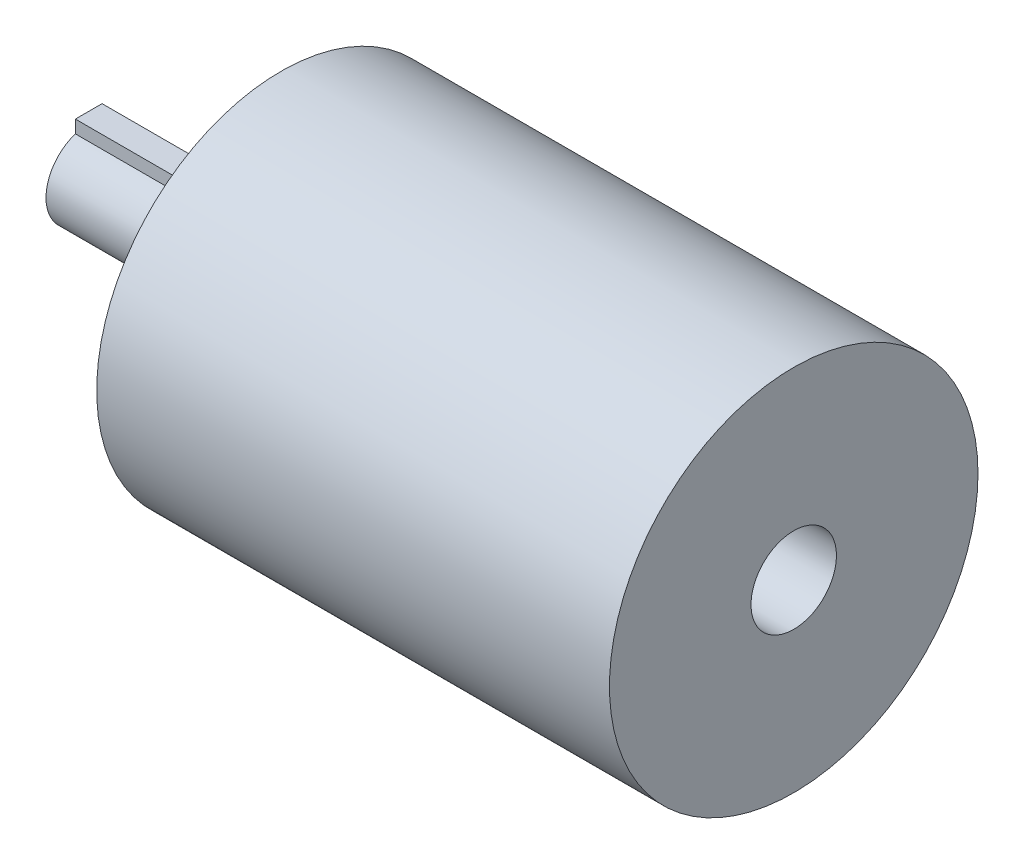
SolidWorks part; units mm, degrees
ref_plane "Front Plane" through (0, 0, 0) normal (0, 0, 1) x (1, 0, 0)
ref_plane "Top Plane" through (0, 0, 0) normal (0, 1, 0) x (1, 0, 0)
ref_plane "Right Plane" through (0, 0, 0) normal (1, 0, 0) x (0, 0, -1)
sketch "Sketch1" plane through (0, 0, 0) normal (1, 0, 0) x (0, 0, -1)
  line L1 (2.5, 10) -> (-2.5, 10)
  line L2 (2.5, 10) -> (2.5, 6)
  line L3 (2.5, 6) -> (-2.5, 6)
  line L4 (-2.5, 10) -> (-2.5, 6)
  line L5 (2.5, 10) -> (-2.5, 6) construction
  line L6 (2.5, 6) -> (-2.5, 10) construction
  circle A0 centre (0, 0) radius 26
  circle A1 centre (0, 0) radius 34.5
  circle A2 centre (0, 0) radius 8
  point P5 (0, 8)
  dimension "D1" = 69
  dimension "D4" = 16
  dimension "D5" = 52
  dimension "D2" = 5
  dimension "D3" = 4
extrude "Boss-Extrude1" add sketch "Sketch1" against normal blind 36 and the other way blind 10 contours L4 A2 L2 L3 | A2 L2 L1 L4 | L2 A2 L4 L3 region at (0, 8.9306, 0) region at (0, -0.3379, 0) region at (0, 6.9377, 0)
extrude "Boss-Extrude2" add sketch "Sketch1<3>" against normal blind 4.5 contours A0 A2 L4 L1 L2 region at (0, 0, 25.2646)
sketch "Sketch1<3>" plane through (0, 0, 0) normal (1, 0, 0) x (0, 0, -1) same geometry as "Sketch1"
extrude "Boss-Extrude3" add sketch "Sketch1<4>" along normal blind 96 separate body contours A1 A0 | A0 A2 L4 L1 L2 | A2 L2 L1 L4 region at (0, 8.9306, 0) region at (0, 0, 25.2646) region at (0, 0, 33.5242)
sketch "Sketch1<4>" plane through (0, 0, 0) normal (1, 0, 0) x (0, 0, -1) same geometry as "Sketch1"
ref_plane "Plane1" through (96, 0, 0) normal (1, 0, 0) x (0, 0, -1)
hole_wizard "M5 Tapped Hole1" positions "Sketch2" profile "Sketch3" tap size "M5" standard "ISO"
sketch "Sketch2" plane through (0, 0, 0) normal (-1, 0, 0) x (0, 0, 1)
  line L0 (0, 0) -> (0, 38.7909) construction
  line L1 (0, 38.7909) -> (0, -41.4441) construction
  line L2 (0, -41.4441) -> (0, 0) construction
  line L3 (0, 0) -> (63.4132, 0) construction
  line L4 (63.4132, 0) -> (-46.6445, 0) construction
  circle A0 centre (0, 0) radius 31
  point P0 (0, 31)
  point P2 (-31, 0)
  point P4 (0, -31)
  point P6 (31, 0)
  point P37 (0, 31)
  point P38 (31, 0)
  point P39 (0, -31)
  point P40 (-31, 0)
  dimension "D1" = 62
sketch "Sketch3" plane through (0, 31, 0) normal (0, 1, 0) x (0, 0, 1)
  line L0 (0, 0) -> (0, 13.6618)
  line L1 (0, 13.6618) -> (2.1, 12.4)
  line L2 (2.1, 12.4) -> (2.1, 0)
  line L5 (2.1, 0) -> (0, 0)
  line L10 (0, 13.6618) -> (-2.1, 12.4) construction
  line L11 (0, -6.35) -> (0, 107.95) construction
  dimension "Tap Drill Dia." = 4.2
  dimension "Tap Drill Depth" = 12.4
  dimension "Drill Angle" = 118
cosmetic thread "Hole Thread5"
cosmetic thread "Hole Thread6"
cosmetic thread "Hole Thread7"
cosmetic thread "Hole Thread8"
